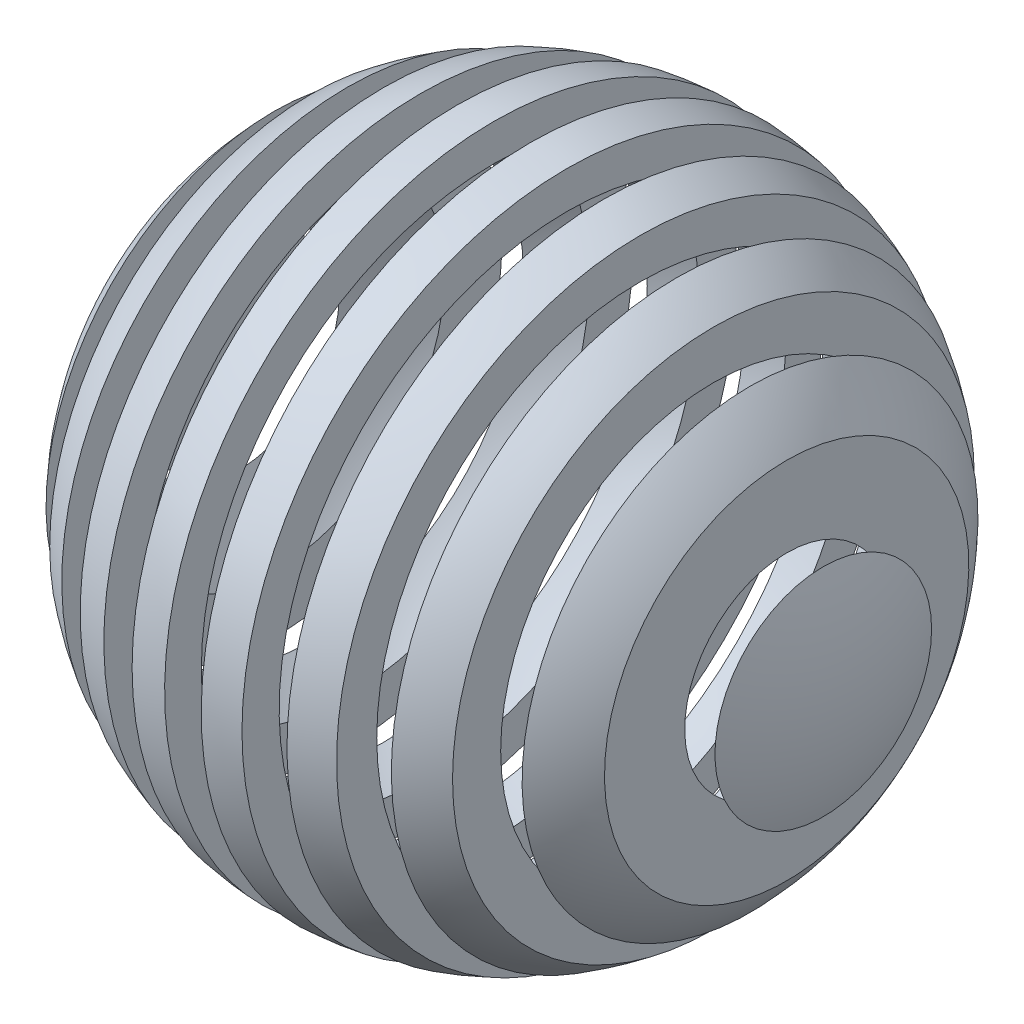
SolidWorks part; units mm, degrees
note: '?' marks a value the reader was unsure of.
material "Galvanized Steel"
ref_plane "Front Plane" through (0, 0, 0) normal (0, 0, 1) x (1, 0, 0)
ref_plane "Top Plane" through (0, 0, 0) normal (0, 1, 0) x (1, 0, 0)
ref_plane "Right Plane" through (0, 0, 0) normal (1, 0, 0) x (0, 0, -1)
sketch "Sketch1" plane through (0, 0, 0) normal (0, 0, 1) x (1, 0, 0)
  line L2 (-450, 0) -> (-400, 0)
  line L3 (400, 0) -> (450, 0)
  arc A0 (-450, 0) -> (450, 0) centre (0, 0) cw
  arc A1 (-400, 0) -> (400, 0) centre (0, 0) cw
  point P4 (0, 0)
  dimension "D2" = 400
  dimension "D3" = 50
  dimension "D1" = 450
  dimension "D4" = 900
  dimension "D5" = 50
ref_axis "Axis1" through (-450, 0, 0) along (1, 0, 0)
revolve "Revolve2" add sketch "Sketch1" angle 360 about axis through (-450, 0, 0) along (1, 0, 0)
ref_plane "Plane1" through (0, 0, 450) normal (0, 0, 1) x (1, 0, 0)
ref_axis "Axis4" through (0, 0, -495) along (0, 0, 1)?
sketch "Sketch2" plane through (0, 0, 0) normal (0, 0, 1) x (1, 0, 0)
  line L1 (-25, -488.1452) -> (25, -488.1452)
  line L2 (-25, -488.1452) -> (-25, 488.1452)
  line L3 (-25, 488.1452) -> (25, 488.1452)
  line L4 (25, -488.1452) -> (25, 488.1452)
  line L5 (-25, -488.1452) -> (25, 488.1452) construction
  line L6 (-25, 488.1452) -> (25, -488.1452) construction
  point P0 (0, 0)
  dimension "D1" = 50
extrude "Cut-Extrude1" cut sketch "Sketch2" against normal through all and the other way through all
pattern_linear "LPattern1" count 5 spacing 100 along (-1, 0, 0) count 5 spacing 100 along (1, 0, 0) of "Cut-Extrude1"
